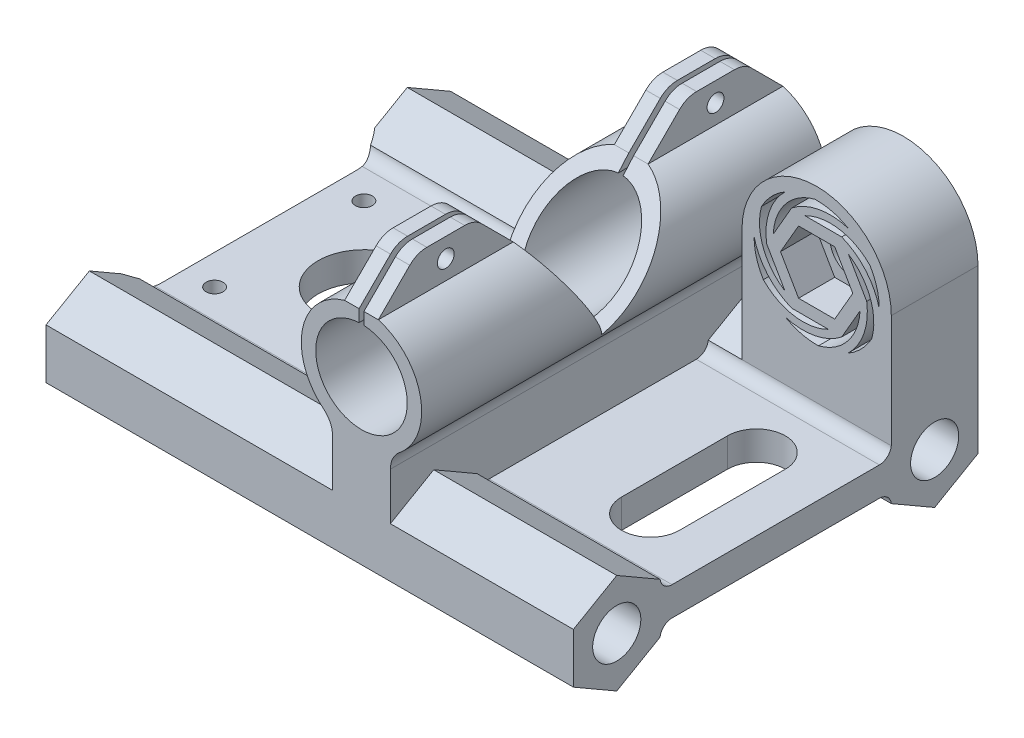
SolidWorks part; units mm, degrees
ref_plane "Front Plane" through (0, 0, 0) normal (0, 0, 1) x (1, 0, 0)
ref_plane "Top Plane" through (0, 0, 0) normal (0, 1, 0) x (1, 0, 0)
ref_plane "Right Plane" through (0, 0, 0) normal (1, 0, 0) x (0, 0, -1)
sketch "Sketch2" plane through (0, 0, 0) normal (1, 0, 0) x (0, 0, -1)
  line L0 (-7.6113, 0) -> (58.3887, 0) construction
  line L1 (1.3887, 3) -> (49.3887, 3)
  line L2 (67.3887, 5.1962) -> (58.3887, 10.3923)
  line L3 (58.3887, 10.3923) -> (49.3887, 5.1962)
  line L4 (49.3887, 5.1962) -> (49.3887, 3)
  line L5 (49.3887, -5.1962) -> (58.3887, -10.3923)
  line L6 (58.3887, -10.3923) -> (67.3887, -5.1962)
  line L7 (67.3887, -5.1962) -> (67.3887, 5.1962)
  line L8 (1.3887, 5.1962) -> (-7.6113, 10.3923)
  line L9 (-7.6113, 10.3923) -> (-16.6113, 5.1962)
  line L10 (-16.6113, 5.1962) -> (-16.6113, -5.1962)
  line L11 (-16.6113, -5.1962) -> (-7.6113, -10.3923)
  line L12 (-7.6113, -10.3923) -> (1.3887, -5.1962)
  line L13 (1.3887, -5.1962) -> (1.3887, -3)
  line L14 (1.3887, -3) -> (49.3887, -3)
  line L15 (49.3887, -3) -> (49.3887, -5.1962)
  line L16 (1.3887, 3) -> (1.3887, 5.1962)
  circle A2 centre (58.3887, 0) radius 9 construction
  circle A3 centre (-7.6113, 0) radius 9 construction
  dimension "D2" = 18
  dimension "D3" = 48
  dimension "D4" = 6
  dimension "D5" = 3
extrude "Boss-Extrude1" add sketch "Sketch2" along normal blind 109.5
sketch "Sketch3" plane through (0, 3, 0) normal (0, 1, 0) x (1, 0, 0)
  line L0 (0, 49.3887) -> (48, 1.3887) construction
  line L1 (109.5, 1.3887) -> (0, 1.3887) construction
  line L2 (0, 1.3887) -> (48, 49.3887) construction
  line L3 (109.5, 49.3887) -> (0, 49.3887) construction
  line L4 (109.5, 1.3887) -> (0, 1.3887) construction
  line L5 (2.25, 47.1387) -> (2.25, 1.3887)
  line L6 (39.5, 40.8887) -> (8.5, 40.8887) construction
  line L7 (39.5, 40.8887) -> (39.5, 9.8887) construction
  line L8 (39.5, 9.8887) -> (8.5, 9.8887) construction
  line L9 (8.5, 40.8887) -> (8.5, 9.8887) construction
  line L10 (2.25, 47.1387) -> (45.75, 47.1387) construction
  line L11 (45.75, 47.1387) -> (45.75, 3.6387) construction
  line L12 (45.75, 3.6387) -> (2.25, 3.6387) construction
  line L13 (2.25, 1.3887) -> (0, -0.8613)
  line L14 (0, 1.3887) -> (0, -7.6113) construction
  line L16 (2.25, 47.1387) -> (2.25, 49.3887)
  line L18 (2.25, 49.3887) -> (0, 51.6387)
  line L20 (0, 58.3887) -> (0, 49.3887) construction
  line L21 (0, 51.6387) -> (0, -0.8613)
  circle A0 centre (24, 25.3887) radius 9.5
  circle A1 centre (39.5, 40.8887) radius 1.75
  circle A2 centre (39.5, 9.8887) radius 1.75
  circle A3 centre (8.5, 9.8887) radius 1.75
  circle A4 centre (8.5, 40.8887) radius 1.75
  dimension "D4" = 3.5
  dimension "D5" = 19
  dimension "D1" = 45
  dimension "D2" = 45
  dimension "D3" = 31
  dimension "D6" = 43.5
extrude "Cut-Extrude1" cut sketch "Sketch3" against normal blind 28 and the other way blind 30
fillet "Fillet3" radius 2.5 4 edges at (55.875, -3, -1.3887) (55.875, -3, -49.3887) (55.875, 3, -49.3887) (55.875, 3, -1.3887)
sketch "Sketch4" plane through (0, 0, -67.3887) normal (0, 0, -1) x (-1, 0, 0)
  line L0 (-65.5, 3) -> (-65.5, 28.6118) construction
  line L1 (-109.5, 3) -> (-2.25, 3) construction
  line L2 (-41.25, 3) -> (-41.25, -3) construction
  line L3 (-71.5, 3) -> (-71.5, 17.6459)
  line L4 (-59.5, 3) -> (-59.5, 17.6459)
  line L5 (-59.5, 3) -> (-71.5, 3)
  line L6 (-62, 40.6118) -> (-62, 48.6118)
  line L7 (-62, 48.6118) -> (-65, 48.6118)
  line L8 (-65, 48.6118) -> (-65, 41.1018)
  line L9 (-69, 48.6118) -> (-66, 48.6118)
  line L10 (-66, 48.6118) -> (-66, 41.1018)
  line L11 (-69, 40.6118) -> (-69, 48.6118)
  line L12 (-66, 41.1018) -> (-66, 38.0986)
  line L13 (-65, 41.1018) -> (-65, 38.0986)
  arc A0 (-66, 38.0986) -> (-65, 38.0986) centre (-65.5, 28.6118) ccw
  arc A1 (-59.5, 17.6459) -> (-62, 40.6118) centre (-65.5, 28.6118) ccw
  arc A3 (-69, 40.6118) -> (-71.5, 17.6459) centre (-65.5, 28.6118) ccw
  dimension "D1" = 19
  dimension "D2" = 25
  dimension "D3" = 24.25
  dimension "D4" = 12
  dimension "D5" = 6
  dimension "D6" = 3
  dimension "D7" = 0.5
  dimension "D8" = 8
extrude "Boss-Extrude2" add sketch "Sketch4" against normal up to surface (84 mm away) up to face at (54.75, 0, 16.6113)
fillet "Fillet4" radius 5 2 edges at (59.5, 17.6459, -25.3887) (71.5, 17.6459, -25.3887)
sketch "Sketch5" plane through (0, 0, -67.3887) normal (0, 0, -1) x (-1, 0, 0)
  line L0 (-65.5, 28.6118) -> (-110, 28.6118) construction
  line L1 (-109.5, 28.6118) -> (-109.5, 5.1962)
  line L2 (-109.5, 5.1962) -> (-71.5, 5.1962) construction
  line L3 (-109.5, 5.1962) -> (-78.5, 5.1962)
  line L4 (-78.5, 5.1962) -> (-78.5, 28.6118)
  circle A0 centre (-94, 28.6118) radius 4.75
  arc A1 (-78.5, 28.6118) -> (-109.5, 28.6118) centre (-94, 28.6118) ccw
  dimension "D1" = 9.5
  dimension "D3" = 31
  dimension "D2" = 28.5
extrude "Boss-Extrude7" add sketch "Sketch5" against normal up to vertex (18 mm away) up to point (71.5, 5.1962, -49.3887)
sketch "Sketch6" plane through (0, 0, -49.3887) normal (0, 0, 1) x (1, 0, 0)
  line L1 (101.5056, 28.6118) -> (97.7528, 35.1118)
  line L2 (97.7528, 35.1118) -> (90.2472, 35.1118)
  line L3 (90.2472, 35.1118) -> (86.4944, 28.6118)
  line L4 (86.4944, 28.6118) -> (90.2472, 22.1118)
  line L5 (90.2472, 22.1118) -> (97.7528, 22.1118)
  line L6 (97.7528, 22.1118) -> (101.5056, 28.6118)
  circle A0 centre (94, 28.6118) radius 6.5 construction
  dimension "D1" = 13
extrude "Cut-Extrude2" cut sketch "Sketch6" against normal blind 7.5
sketch "Sketch7" plane through (0, 0, 0) normal (-1, 0, 0) x (0, 0, 1)
  line L0 (-67.3887, 18.8899) -> (16.6113, 18.8899) construction
  line L1 (-67.3887, 40.6118) -> (-39.3887, 40.6118) construction
  line L2 (-67.3887, 40.6118) -> (-67.3887, 18.8899) construction
  line L3 (-67.3887, 18.8899) -> (-39.3887, 18.8899) construction
  line L4 (-39.3887, 40.6118) -> (-39.3887, 18.8899) construction
  line L5 (16.6113, 40.6118) -> (-67.3887, 40.6118) construction
  line L6 (16.6113, 18.8899) -> (-11.3887, 18.8899) construction
  line L7 (16.6113, 18.8899) -> (16.6113, 40.6118) construction
  line L8 (16.6113, 40.6118) -> (-11.3887, 40.6118) construction
  line L9 (-11.3887, 18.8899) -> (-11.3887, 40.6118) construction
  line L10 (16.6113, 44.6118) -> (-67.3887, 44.6118) construction
  line L11 (16.6113, 48.6118) -> (16.6113, 40.6118) construction
  line L12 (-67.3887, 40.6118) -> (-67.3887, 48.6118) construction
  line L13 (-53.3887, 40.6118) -> (-53.3887, 48.6118) construction
  line L14 (16.6113, 48.6118) -> (-67.3887, 48.6118) construction
  line L15 (2.6113, 40.6118) -> (2.6113, 48.6118) construction
  line L16 (-39.3887, 40.6118) -> (-22.8887, 21.6118)
  line L17 (-11.3887, 40.6118) -> (-22.8887, 21.6118)
  line L18 (-11.3887, 40.6118) -> (-11.3887, 48.6118)
  line L19 (-39.3887, 40.6118) -> (-39.3887, 48.6118)
  line L20 (-39.3887, 48.6118) -> (-11.3887, 48.6118)
  circle A0 centre (2.6113, 44.6118) radius 1.75
  circle A1 centre (-53.3887, 44.6118) radius 1.75
  dimension "D3" = 3.5
  dimension "D1" = 28
  dimension "D2" = 28
extrude "Cut-Extrude3" cut sketch "Sketch7" against normal up to surface (78.5 mm away) up to face at (78.5, 15.6016, -58.3887)
chamfer "Chamfer1" distance 8 angle 45 8 edges at (67.5, 48.6118, -67.3887) (63.5, 48.6118, -67.3887) (67.5, 48.6118, -11.3887) (63.5, 48.6118, -11.3887) (63.5, 48.6118, -39.3887) (67.5, 48.6118, -39.3887) (67.5, 48.6118, 16.6113) (63.5, 48.6118, 16.6113)
fillet "Fillet5" radius 5 8 edges at (63.5, 48.6118, -59.3887) (67.5, 48.6118, -59.3887) (67.5, 48.6118, -47.3887) (63.5, 48.6118, -47.3887) (67.5, 48.6118, -3.3887) (63.5, 48.6118, -3.3887) (67.5, 48.6118, 8.6113) (63.5, 48.6118, 8.6113)
sketch "Sketch9" plane through (109.5, 0, 0) normal (1, 0, 0) x (0, 0, -1)
  line L0 (-12.1113, 7.7942) -> (-3.1113, -7.7942) construction
  line L1 (-7.6113, 10.3923) -> (-16.6113, 5.1962) construction
  line L2 (-7.6113, -10.3923) -> (1.3887, -5.1962) construction
  line L3 (53.8887, -7.7942) -> (62.8887, 7.7942) construction
  line L4 (49.3887, -5.1962) -> (58.3887, -10.3923) construction
  circle A0 centre (58.3887, 0) radius 5
  circle A1 centre (-7.6113, 0) radius 5
  dimension "D1" = 10
extrude "Cut-Extrude5" cut sketch "Sketch9" against normal up to surface (50 mm away) up to face at (59.5, 7.6631, -25.3887)
sketch "Sketch11" plane through (0, 0, -49.3887) normal (0, 0, 1) x (1, 0, 0)
  line L0 (97.7528, 35.1118) -> (90.2472, 35.1118) construction
  line L1 (99.1962, 19.6118) -> (104.3923, 28.6118) construction
  line L2 (104.3923, 28.6118) -> (99.1962, 37.6118) construction
  line L3 (99.1962, 37.6118) -> (88.8038, 37.6118) construction
  line L4 (88.8038, 37.6118) -> (83.6077, 28.6118) construction
  line L5 (83.6077, 28.6118) -> (88.8038, 19.6118) construction
  line L6 (88.8038, 19.6118) -> (99.1962, 19.6118) construction
  line L7 (97.7528, 35.1118) -> (90.2472, 35.1118) construction
  line L8 (100.5759, 35.2221) -> (104.3923, 28.6118)
  line L9 (103.0126, 26.2221) -> (99.1962, 19.6118)
  line L10 (96.4367, 19.6118) -> (88.8038, 19.6118)
  line L11 (87.4241, 22.0015) -> (83.6077, 28.6118)
  line L12 (84.9874, 31.0015) -> (88.8038, 37.6118)
  line L13 (91.5633, 37.6118) -> (99.1962, 37.6118)
  arc A0 (100.5, 39.8701) -> (93.6243, 41.6064) centre (94, 28.6118) ccw construction
  arc A1 (109.5, 28.6118) -> (78.5, 28.6118) centre (94, 28.6118) ccw construction
  circle A2 centre (94, 28.6118) radius 9 construction
  arc A3 (99.1962, 37.6118) -> (107, 28.6118) centre (94.3677, 25.5417) cw
  arc A4 (100.5, 39.8701) -> (93.6243, 41.6064) centre (94, 28.6118) ccw
  arc A5 (104.3923, 28.6118) -> (100.5, 17.3535) centre (91.5251, 26.7583) cw
  arc A6 (105.4415, 22.4399) -> (100.5759, 35.2221) centre (94.3677, 25.5417) ccw
  arc A7 (94.3757, 15.6172) -> (103.0126, 26.2221) centre (91.5251, 26.7583) ccw
  arc A8 (99.1962, 19.6118) -> (87.5, 17.3535) centre (91.1574, 29.8284) cw
  arc A9 (82.9342, 21.7891) -> (96.4367, 19.6118) centre (91.1574, 29.8284) ccw
  arc A10 (88.8038, 19.6118) -> (81, 28.6118) centre (93.6323, 31.6818) cw
  arc A11 (82.5585, 34.7837) -> (87.4241, 22.0015) centre (93.6323, 31.6818) ccw
  arc A12 (83.6077, 28.6118) -> (87.5, 39.8701) centre (96.4749, 30.4653) cw
  arc A13 (93.6243, 41.6064) -> (84.9874, 31.0015) centre (96.4749, 30.4653) ccw
  arc A14 (88.8038, 37.6118) -> (100.5, 39.8701) centre (96.8426, 27.3952) cw
  arc A15 (105.0658, 35.4344) -> (91.5633, 37.6118) centre (96.8426, 27.3952) ccw
  arc A16 (87.5, 39.8701) -> (82.5585, 34.7837) centre (94, 28.6118) ccw construction
  arc A17 (87.5, 39.8701) -> (82.5585, 34.7837) centre (94, 28.6118) ccw
  arc A18 (81, 28.6118) -> (82.9342, 21.7891) centre (94, 28.6118) ccw construction
  arc A19 (81, 28.6118) -> (82.9342, 21.7891) centre (94, 28.6118) ccw
  arc A20 (87.5, 17.3535) -> (94.3757, 15.6172) centre (94, 28.6118) ccw construction
  arc A21 (87.5, 17.3535) -> (94.3757, 15.6172) centre (94, 28.6118) ccw
  arc A22 (100.5, 17.3535) -> (105.4415, 22.4399) centre (94, 28.6118) ccw construction
  arc A23 (100.5, 17.3535) -> (105.4415, 22.4399) centre (94, 28.6118) ccw
  arc A24 (107, 28.6118) -> (105.0658, 35.4344) centre (94, 28.6118) ccw construction
  arc A25 (107, 28.6118) -> (105.0658, 35.4344) centre (94, 28.6118) ccw
  point P55 (94, 28.6118)
  dimension "D1" = 2.5
  dimension "D3" = 6
  dimension "D2" = 2.5
extrude "Cut-Extrude7" cut sketch "Sketch11" against normal up to surface (18 mm away) up to face at (64.5556, 20.7564, -67.3887)
sketch "Sketch14" plane through (0, 3, 0) normal (0, 1, 0) x (1, 0, 0)
  line L0 (94.5, 67.3887) -> (94.5, -16.6113) construction
  line L3 (109.5, 46.9073) -> (109.5, 3.8702) construction
  line L4 (94.5, 36.3887) -> (94.5, 14.3887) construction
  line L5 (100.5, 36.3887) -> (100.5, 14.3887)
  line L6 (88.5, 36.3887) -> (88.5, 14.3887)
  line L8 (109.5, -16.6113) -> (71.5, -16.6113) construction
  arc A0 (100.5, 36.3887) -> (88.5, 36.3887) centre (94.5, 36.3887) ccw
  arc A1 (88.5, 14.3887) -> (100.5, 14.3887) centre (94.5, 14.3887) ccw
  point P10 (94.5, 25.3887)
  dimension "D2" = 6
  dimension "D1" = 15
  dimension "D3" = 22
extrude "Cut-Extrude8" cut sketch "Sketch14" against normal blind 10
fillet "Fillet7" radius 10 2 edges at (2.25, 0, -1.3887) (2.25, 0, -49.3887)
